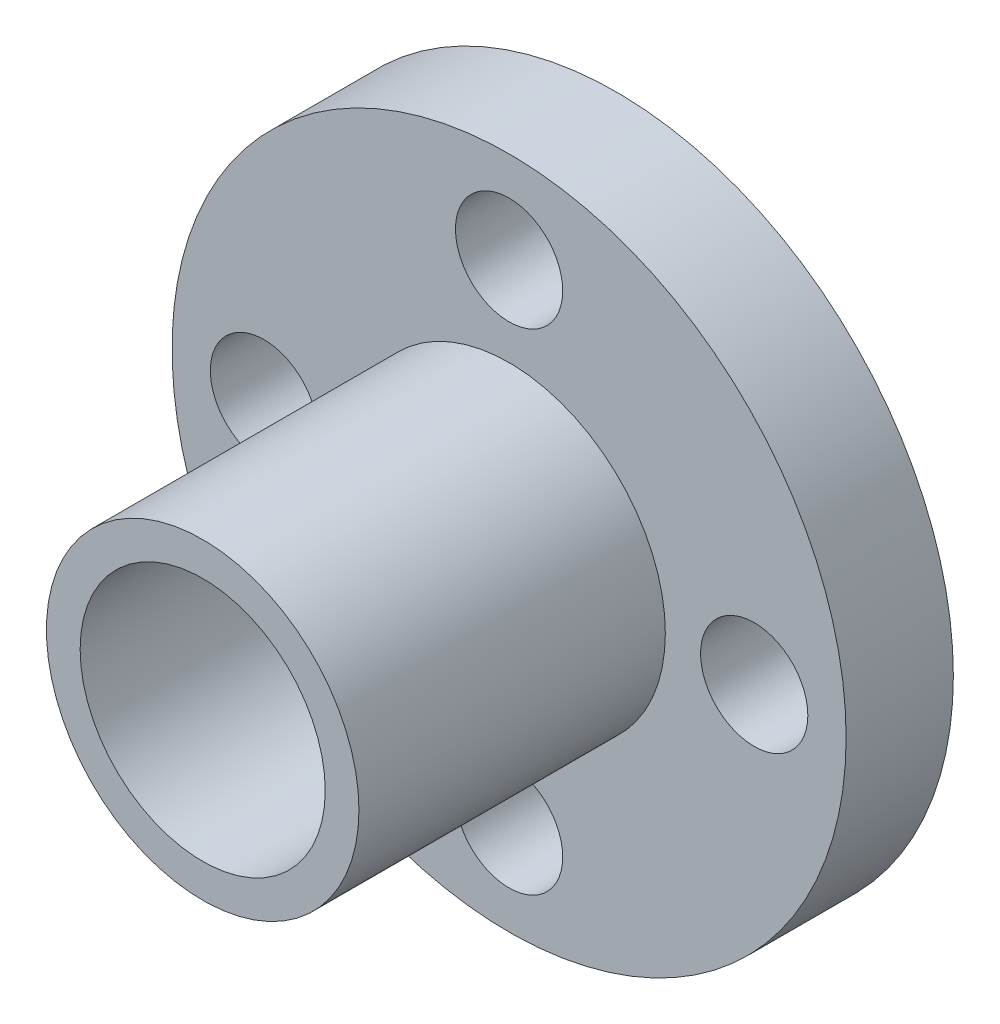
SolidWorks part; units mm, degrees
ref_plane "Front Plane" through (0, 0, 0) normal (0, 0, 1) x (1, 0, 0)
ref_plane "Top Plane" through (0, 0, 0) normal (0, 1, 0) x (1, 0, 0)
ref_plane "Right Plane" through (0, 0, 0) normal (1, 0, 0) x (0, 0, -1)
sketch "Sketch1" plane through (0, 0, 0) normal (0, 0, 1) x (1, 0, 0)
  circle A0 centre (0, 0) radius 11
  circle A1 centre (0, 0) radius 5.1
  circle A2 centre (0, 0) radius 4
  dimension "D1" = 8
  dimension "D2" = 10.2
  dimension "D3" = 22
extrude "Boss-Extrude1" add sketch "Sketch1" along normal blind 15 contours A1 A2 region at (-4.9558, 0, 0)
extrude "Boss-Extrude2" add sketch "Sketch1<3>" along normal blind 3.5 from offset 1.5 contours A0 A1 region at (-10.6889, 0, 0)
sketch "Sketch1<3>" plane through (0, 0, 0) normal (0, 0, 1) x (1, 0, 0) same geometry as "Sketch1"
sketch "Sketch2" plane through (0, 0, 5) normal (0, 0, 1) x (1, 0, 0)
  line L0 (0, 0) -> (15.7841, 0) construction
  circle A0 centre (8, 0) radius 1.75
  circle A1 centre (0, -8) radius 1.75
  circle A2 centre (-8, 0) radius 1.75
  circle A3 centre (0, 8) radius 1.75
  point P14 (0, 0)
  dimension "D2" = 3.5
  dimension "D1" = 8
  dimension "D3" = 4
extrude "Cut-Extrude1" cut sketch "Sketch2" against normal through all
